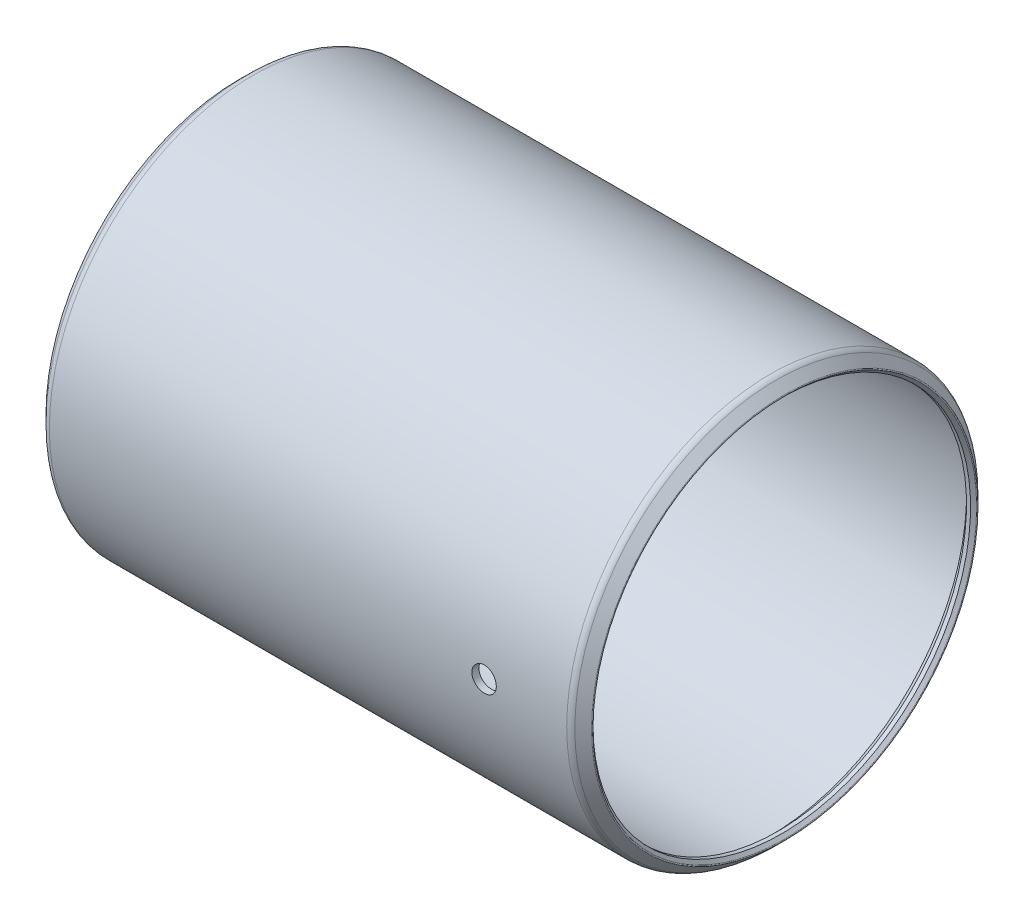
SolidWorks part; units mm, degrees
material "Cast Alloy Steel"
ref_plane "Front Plane" through (0, 0, 0) normal (0, 0, 1) x (1, 0, 0)
ref_plane "Top Plane" through (0, 0, 0) normal (0, 1, 0) x (1, 0, 0)
ref_plane "Right Plane" through (0, 0, 0) normal (1, 0, 0) x (0, 0, -1)
ref_plane "Plane1" through (69.0118, 0, 0) normal (1, 0, 0) x (0, 0, -1)
sketch "Sketch1" plane through (0, 0, 0) normal (0, 0, 1) x (1, 0, 0)
  line L0 (-0.9191, 24.9094) -> (-0.5271, 24.5174)
  line L1 (-0.5271, 24.5174) -> (0, 24.5174)
  line L2 (0, 24.5174) -> (1.0541, 25.5714)
  line L3 (1.0541, 25.5714) -> (67.9577, 25.5714)
  line L4 (67.9577, 25.5714) -> (69.0118, 24.5174)
  line L5 (69.0118, 24.5174) -> (69.5388, 24.5174)
  line L6 (69.5388, 24.5174) -> (69.9309, 24.9094)
  line L7 (69.9309, 25.089) -> (68.8428, 26.1771)
  line L8 (68.0974, 26.4858) -> (0.9144, 26.4858)
  line L9 (0.169, 26.1771) -> (-0.9191, 25.089)
  line L10 (69.0118, 0) -> (0, 0) construction
  arc A0 (-0.9191, 25.089) -> (-0.9191, 24.9094) centre (-0.8293, 24.9992) ccw
  arc A1 (69.9309, 24.9094) -> (69.9309, 25.089) centre (69.8411, 24.9992) ccw
  arc A2 (68.8428, 26.1771) -> (68.0974, 26.4858) centre (68.0974, 25.4317) ccw
  arc A3 (0.9144, 26.4858) -> (0.169, 26.1771) centre (0.9144, 25.4317) ccw
revolve "Revolve1" add sketch "Sketch1" angle 360 about L10 reverse direction yes
sketch "Sketch2" plane through (0, 0, 0) normal (0, 0, 1) x (1, 0, 0)
  circle A0 centre (57.3659, 0) radius 1.5875
extrude "Cut-Extrude1" cut sketch "Sketch2" along normal blind 26.4858
ref_plane "Plane2" through (34.5059, 0, 0) normal (1, 0, 0) x (0, 0, -1)
ref_plane "cp1 XY" through (34.5059, 0, 0) normal (1, 0, 0) x (0, 0, -1)
ref_plane "cp1 XZ" through (0, 26.4858, 0) normal (0, -1, 0) x (-1, 0, 0)
ref_plane "cp1 YZ" through (0, 0, 0) normal (0, 0, -1) x (-1, 0, 0)
ref_axis "cp1 X" through (34.5059, 26.4858, 80.9) along (0, 0, -1)
ref_axis "cp1 Y" through (34.5059, -50, 0) along (0, 1, 0)
ref_axis "cp1 Z" through (80.9, 26.4858, 0) along (-1, 0, 0)
sketch3d "cp1"
  point P0 (34.5059, 26.4858, 0)
ref_plane "cp2 XY" through (34.5059, 0, 0) normal (1, 0, 0) x (0, 0, -1)
ref_plane "cp2 XZ" through (0, 0, 0) normal (0, -1, 0) x (-1, 0, 0)
ref_plane "cp2 YZ" through (0, 0, -26.4858) normal (0, 0, -1) x (-1, 0, 0)
ref_axis "cp2 X" through (34.5059, 0, 80.9) along (0, 0, -1)
ref_axis "cp2 Y" through (34.5059, -50, -26.4858) along (0, 1, 0)
ref_axis "cp2 Z" through (80.9, 0, -26.4858) along (-1, 0, 0)
sketch3d "cp2"
  point P0 (34.5059, 0, -26.4858)
ref_plane "cp3 XY" through (34.5059, 0, 0) normal (1, 0, 0) x (0, 0, -1)
ref_plane "cp3 XZ" through (0, -26.4858, 0) normal (0, -1, 0) x (-1, 0, 0)
ref_plane "cp3 YZ" through (0, 0, 0) normal (0, 0, -1) x (-1, 0, 0)
ref_axis "cp3 X" through (34.5059, -26.4858, 80.9) along (0, 0, -1)
ref_axis "cp3 Y" through (34.5059, -50, 0) along (0, 1, 0)
ref_axis "cp3 Z" through (80.9, -26.4858, 0) along (-1, 0, 0)
sketch3d "cp3"
  point P0 (34.5059, -26.4858, 0)
ref_plane "cp4 XY" through (34.5059, 0, 0) normal (1, 0, 0) x (0, 0, -1)
ref_plane "cp4 XZ" through (0, 0, 0) normal (0, -1, 0) x (-1, 0, 0)
ref_plane "cp4 YZ" through (0, 0, 26.4858) normal (0, 0, -1) x (-1, 0, 0)
ref_axis "cp4 X" through (34.5059, 0, 80.9) along (0, 0, -1)
ref_axis "cp4 Y" through (34.5059, -50, 26.4858) along (0, 1, 0)
ref_axis "cp4 Z" through (80.9, 0, 26.4858) along (-1, 0, 0)
sketch3d "cp4"
  point P0 (34.5059, 0, 26.4858)
ref_plane "tube_front XY" through (0, 0, 0) normal (1, 0, 0) x (0, 0, -1)
ref_plane "tube_front XZ" through (0, 0, 0) normal (0, -1, 0) x (-1, 0, 0)
ref_plane "tube_front YZ" through (0, 0, 0) normal (0, 0, -1) x (-1, 0, 0)
ref_axis "tube_front X" through (0, 0, 80.9) along (0, 0, -1)
ref_axis "tube_front Y" through (0, -50, 0) along (0, 1, 0)
ref_axis "tube_front Z" through (80.9, 0, 0) along (-1, 0, 0)
sketch3d "tube_front"
  point P0 (0, 0, 0)
ref_plane "tube_rear XY" through (69.0118, 0, 0) normal (1, 0, 0) x (0, 0, -1)
ref_plane "tube_rear XZ" through (0, 0, 0) normal (0, -1, 0) x (-1, 0, 0)
ref_plane "tube_rear YZ" through (0, 0, 0) normal (0, 0, -1) x (-1, 0, 0)
ref_axis "tube_rear X" through (69.0118, 0, 80.9) along (0, 0, -1)
ref_axis "tube_rear Y" through (69.0118, -50, 0) along (0, 1, 0)
ref_axis "tube_rear Z" through (80.9, 0, 0) along (-1, 0, 0)
sketch3d "tube_rear"
  point P0 (69.0118, 0, 0)
